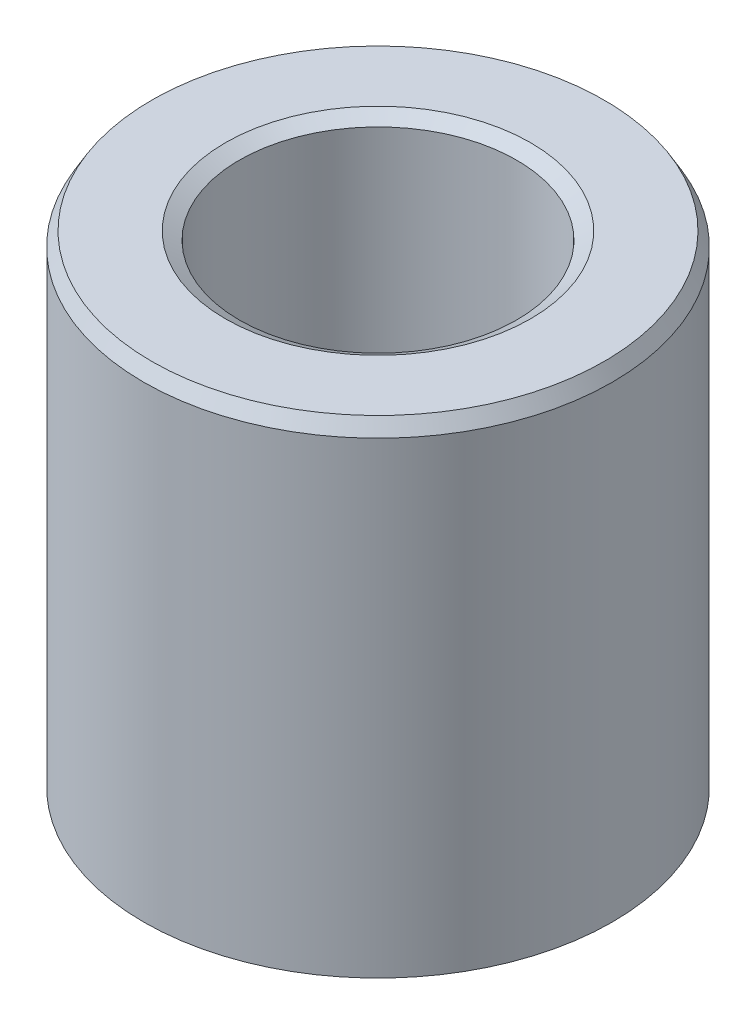
SolidWorks part; units mm, degrees
ref_plane "Front Plane" through (0, 0, 0) normal (0, 0, 1) x (1, 0, 0)
ref_plane "Top Plane" through (0, 0, 0) normal (0, 1, 0) x (1, 0, 0)
ref_plane "Right Plane" through (0, 0, 0) normal (1, 0, 0) x (0, 0, -1)
sketch "Sketch1" plane through (0, 0, 0) normal (0, 1, 0) x (1, 0, 0)
  circle A0 centre (0, 0) radius 10
  dimension "SLEEVE_OD" = 20
extrude "Boss-Extrude1" add sketch "Sketch1" along normal blind 20.891
sketch "Sketch2" plane through (0, 0, 0) normal (0, 1, 0) x (1, 0, 0)
  circle A0 centre (0, 0) radius 5.9142
  dimension "BORE_D" = 11.8285
extrude "Cut-Extrude1" cut sketch "Sketch2" along normal through all
chamfer "Chamfer1" distance 0.5964 angle 30 4 edges at (0, 20.891, 5.9142) (0, 0, 5.9142) (0, 0, 10) (0, 20.891, 10) first distance on face at (0, 20.891, 5.9142) first distance on face at (0, 0, 5.9142) first distance on face at (0, 20.891, 10)
